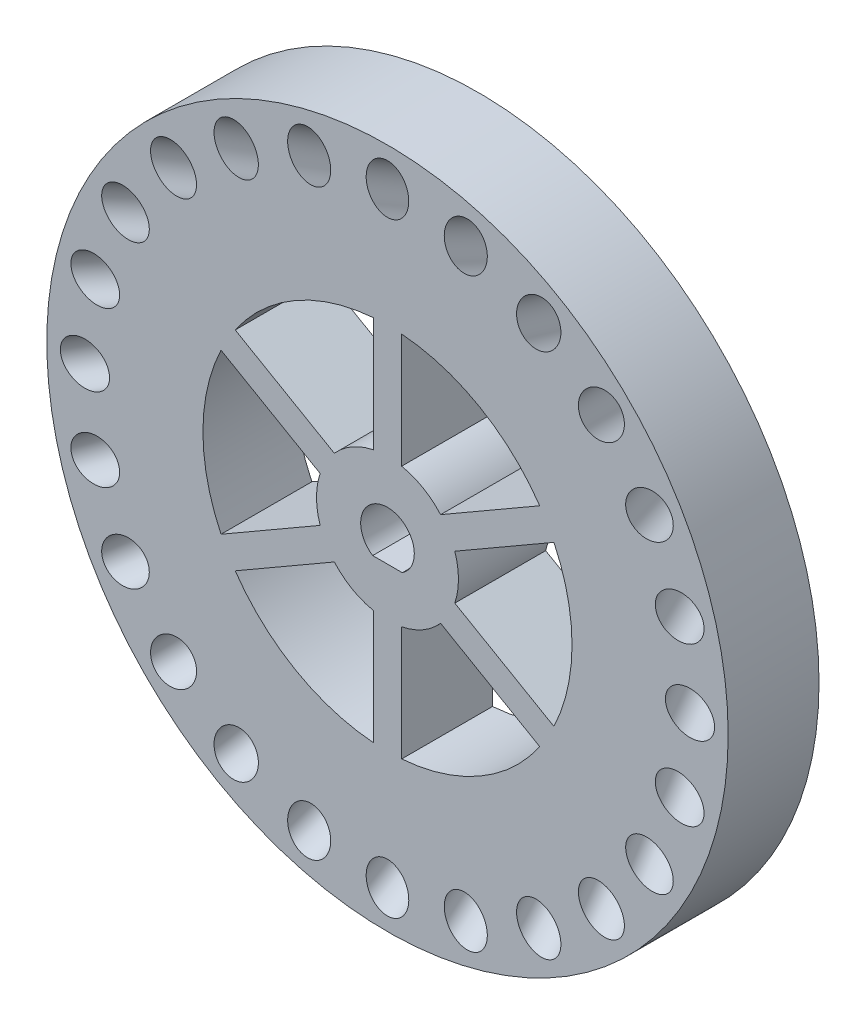
SolidWorks part; units mm, degrees
ref_plane "Front Plane" through (0, 0, 0) normal (0, 0, 1) x (1, 0, 0)
ref_plane "Top Plane" through (0, 0, 0) normal (0, 1, 0) x (1, 0, 0)
ref_plane "Right Plane" through (0, 0, 0) normal (1, 0, 0) x (0, 0, -1)
sketch "Sketch1" plane through (0, 0, 0) normal (0, 0, 1) x (1, 0, 0)
  line L0 (-1.6583, -2.5) -> (1.6583, -2.5)
  arc A0 (1.6583, -2.5) -> (-1.6583, -2.5) centre (0, 0) ccw
  circle A1 centre (0, 0) radius 38.1
  point P1 (0, 38.1)
  dimension "D1" = 6
  dimension "D2" = 76.2
  dimension "D3" = 2.5
extrude "Boss-Extrude1" add sketch "Sketch1" along normal blind 10.16
sketch "Sketch3" plane through (0, 0, 0) normal (1, 0, 0) x (0, 0, -1)
  line L0 (-10.16, 22.098) -> (0, 39.6956)
  line L1 (0, 39.6956) -> (0, 22.098)
  line L2 (0, 22.098) -> (-10.16, 22.098)
  point P0 (-10.16, 0)
  point P4 (-5.08, 30.8968)
  dimension "D1" = 10.16
  dimension "D2" = 10.16
  dimension "D3" = 60
  dimension "D4" = 22.098
  dimension "D5" = 22.098
ref_plane "Plane1" through (0, 9.9239, 17.1887) normal (0, -0.5, -0.866) x (0, 0.866, -0.5)
sketch "Sketch5" plane through (0, 9.9239, 17.1887) normal (0, -0.5, -0.866) x (0, 0.866, -0.5)
  circle A0 centre (24.2174, 0) radius 2.3813
  dimension "D1" = 4.7625
extrude "Cut-Extrude1" cut sketch "Sketch5" against normal through all both and the other way through all
pattern_circular "CirPattern1" count 24 every 15 about axis through (0, 0, 10.16) along (0, 0, -1) of "Cut-Extrude1"
sketch "Sketch6" plane through (0, 0, 0) normal (0, 0, -1) x (-1, 0, 0)
  line L0 (-1.5875, 7.7771) -> (-1.5875, 20.5764)
  line L1 (1.5875, 20.5764) -> (1.5875, 7.7771)
  line L2 (5.9414, 5.2634) -> (17.0259, 11.663)
  line L3 (18.6134, 8.9134) -> (7.5289, 2.5137)
  line L4 (7.5289, -2.5137) -> (18.6134, -8.9134)
  line L5 (17.0259, -11.663) -> (5.9414, -5.2634)
  line L6 (1.5875, -7.7771) -> (1.5875, -20.5764)
  line L7 (-1.5875, -20.5764) -> (-1.5875, -7.7771)
  line L8 (-5.9414, -5.2634) -> (-17.0259, -11.663)
  line L9 (-18.6134, -8.9134) -> (-7.5289, -2.5137)
  line L10 (-7.5289, 2.5137) -> (-18.6134, 8.9134)
  line L11 (-17.0259, 11.663) -> (-5.9414, 5.2634)
  arc A0 (-7.5289, 2.5137) -> (-7.5289, -2.5137) centre (0, 0) ccw
  arc A1 (-18.6134, 8.9134) -> (-18.6134, -8.9134) centre (0, 0) ccw
  arc A2 (-1.5875, 7.7771) -> (-5.9414, 5.2634) centre (0, 0) ccw
  arc A3 (-1.5875, 20.5764) -> (-17.0259, 11.663) centre (0, 0) ccw
  arc A4 (17.0259, 11.663) -> (1.5875, 20.5764) centre (0, 0) ccw
  arc A5 (5.9414, 5.2634) -> (1.5875, 7.7771) centre (0, 0) ccw
  arc A6 (7.5289, -2.5137) -> (7.5289, 2.5137) centre (0, 0) ccw
  arc A7 (1.5875, -7.7771) -> (5.9414, -5.2634) centre (0, 0) ccw
  arc A8 (-5.9414, -5.2634) -> (-1.5875, -7.7771) centre (0, 0) ccw
  arc A9 (-17.0259, -11.663) -> (-1.5875, -20.5764) centre (0, 0) ccw
  arc A10 (1.5875, -20.5764) -> (17.0259, -11.663) centre (0, 0) ccw
  arc A11 (18.6134, -8.9134) -> (18.6134, 8.9134) centre (0, 0) ccw
  point P31 (0, 0)
  dimension "D1" = 15.875
  dimension "D2" = 41.275
  dimension "D3" = 3.175
  dimension "D4" = 1.5875
  dimension "D5" = 6
extrude "Cut-Extrude7" cut sketch "Sketch6" against normal blind 17.78
